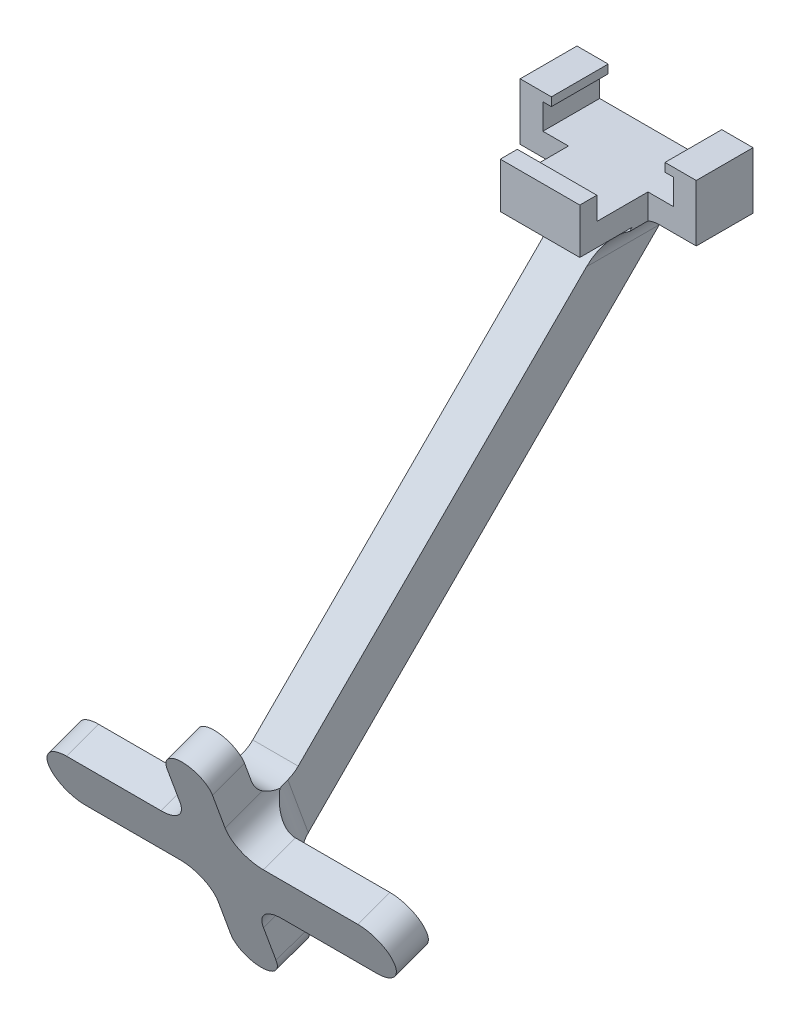
SolidWorks part; units mm, degrees
ref_plane "Front Plane" through (0, 0, 0) normal (0, 0, 1) x (1, 0, 0)
ref_plane "Top Plane" through (0, 0, 0) normal (0, 1, 0) x (1, 0, 0)
ref_plane "Right Plane" through (0, 0, 0) normal (1, 0, 0) x (0, 0, -1)
sketch "Sketch1" plane through (0, 0, 0) normal (0, 0, 1) x (1, 0, 0)
  line L0 (0, 0) -> (0, -9)
  line L1 (0, -9) -> (31, -9)
  line L2 (31, -9) -> (31, 0)
  line L4 (27, -0.5) -> (27, -5)
  line L5 (27, -5) -> (4, -5)
  line L6 (4, -5) -> (4, -0.5)
  line L8 (0, 0) -> (0, 1)
  line L9 (0, 1) -> (5.5, 1)
  line L10 (5.5, 1) -> (5.5, -0.5)
  line L11 (5.5, -0.5) -> (4, -0.5)
  line L12 (15.5, -9) -> (15.5, 2.6509) construction
  line L13 (0, 0) -> (0, 1)
  line L14 (31, 0) -> (31, 1)
  line L15 (25.5, -0.5) -> (27, -0.5)
  line L16 (25.5, 1) -> (25.5, -0.5)
  line L17 (31, 1) -> (25.5, 1)
  dimension "D1" = 23
  dimension "D3" = 4
  dimension "D5" = 1.5
  dimension "D7" = 5.5
extrude "Boss-Extrude1" add sketch "Sketch1" along normal blind 10 contours L1 L12 L5 L6 L11 L10 L9 L8 L0 | L12 L1 L2 L14 L17 L16 L15 L4 L5 region at (6.1098, -5.4554, 0) region at (24.8902, -5.4554, 0)
ref_plane "Plane1" through (15.5, 0, 0) normal (-1, 0, 0) x (0, 0, 1)
sketch "Sketch2" plane through (15.5, 0, 0) normal (-1, 0, 0) x (0, 0, 1)
  line L0 (0, -9) -> (70.7107, -79.7107)
  line L1 (70.7107, -79.7107) -> (74.1309, -70.3138)
  line L2 (74.1309, -70.3138) -> (12.8171, -9)
  line L3 (10, -9) -> (0, -9) construction
  line L4 (74.1309, -70.3138) -> (74.1309, -99.7264) construction
  line L5 (74.1309, -70.3138) -> (74.1309, -44.9818) construction
  line L6 (70.7107, -79.7107) -> (70.7107, -67.2547) construction
  line L11 (0, 1) -> (0, -9)
  line L12 (0, -9) -> (10, -9)
  line L13 (10, -9) -> (10, 1)
  line L14 (10, 1) -> (0, 1)
  line L16 (0, -9) -> (12.8171, -9)
  dimension "D1" = 20
  dimension "D2" = 45
  dimension "D3" = 45
  dimension "D5" = 100
  dimension "D6" = 10
  dimension "D4" = 0
extrude "Boss-Extrude2" add sketch "Sketch2" along normal mid plane 8
sketch "Sketch9" plane through (0, -9, 0) normal (0, 1, 0) x (1, 0, 0)
  line L0 (8.5, -10) -> (8.5, -19)
  line L1 (27, -10) -> (4, -10) construction
  line L2 (8.5, -19) -> (22.5, -19)
  line L3 (22.5, -19) -> (22.5, -10)
  line L4 (22.5, -10) -> (8.5, -10)
  line L5 (15.5, -10) -> (15.5, -19) construction
  line L6 (27, 0) -> (4, 0) construction
  point P10 (15.5, 0)
  dimension "D1" = 9
  dimension "D2" = 7
  dimension "D3" = 7
extrude "Boss-Extrude11" add sketch "Sketch9" along normal blind 4
sketch "Sketch10" plane through (0, 0, 19) normal (0, 0, 1) x (1, 0, 0)
  line L1 (8.5, -9) -> (22.5, -9)
  line L2 (8.5, -9) -> (8.5, -1)
  line L3 (8.5, -1) -> (22.5, -1)
  line L4 (22.5, -9) -> (22.5, -1)
  dimension "D1" = 8
extrude "Boss-Extrude12" add sketch "Sketch10" along normal blind 3
sketch "Sketch11" plane through (0, -32.0504, 88.0576) normal (0, -0.342, 0.9397) x (1, 0, 0)
  line L0 (15.5, -40.7191) -> (15.5, -45.7191) construction
  line L3 (11.5, -40.7191) -> (19.5, -40.7191) construction
  line L12 (11.5, -50.7191) -> (19.5, -50.7191) construction
  line L13 (11.5113, -45.7191) -> (19.4887, -45.7191) construction
  line L14 (-10.1231, -40.8587) -> (11.5113, -40.8587)
  line L15 (-10.1231, -50.5794) -> (11.5113, -50.5794)
  line L16 (15.5, -50.7191) -> (15.5, -50.5794) construction
  line L17 (11.5113, -62.0882) -> (11.5113, -50.5794)
  line L18 (19.4887, -62.0882) -> (19.4887, -50.5794)
  line L19 (19.4887, -40.8587) -> (41.1231, -40.8587)
  line L20 (11.5113, -40.8587) -> (11.5113, -29.3499)
  line L21 (15.5, -50.5794) -> (15.5, -50.7191) construction
  line L22 (15.5, -45.7191) -> (15.5, -44.2584) construction
  line L23 (19.4887, -40.8587) -> (19.4887, -29.3499)
  line L24 (19.4887, -50.5794) -> (41.1231, -50.5794)
  arc A4 (-10.1231, -40.8587) -> (-10.1231, -50.5794) centre (-10.1231, -45.7191) ccw
  arc A5 (41.1231, -50.5794) -> (41.1231, -40.8587) centre (41.1231, -45.7191) ccw
  arc A6 (11.5113, -62.0882) -> (19.4887, -62.0882) centre (15.5, -62.0882) ccw
  arc A7 (19.4887, -29.3499) -> (11.5113, -29.3499) centre (15.5, -29.3499) ccw
  point P8 (15.5, -45.7191)
  point P15 (15.5, -45.7191)
extrude "Boss-Extrude13" add sketch "Sketch11" along normal blind 6
fillet "Fillet8" radius 5 4 edges at (19.4887, -71.471, 76.9022) (19.4887, -80.6055, 73.5775) (11.5113, -80.6055, 73.5775) (11.5113, -71.471, 76.9022)
fillet "Fillet9" radius 5 4 edges at (15.5, -70.3138, 74.1309) (15.5, -79.7107, 70.7107) (11.5, -75.0122, 72.4208) (19.5, -75.0122, 72.4208)
fillet "Fillet10" radius 5 2 edges at (19.5, -9, 6.4086) (11.5, -9, 6.4086)
